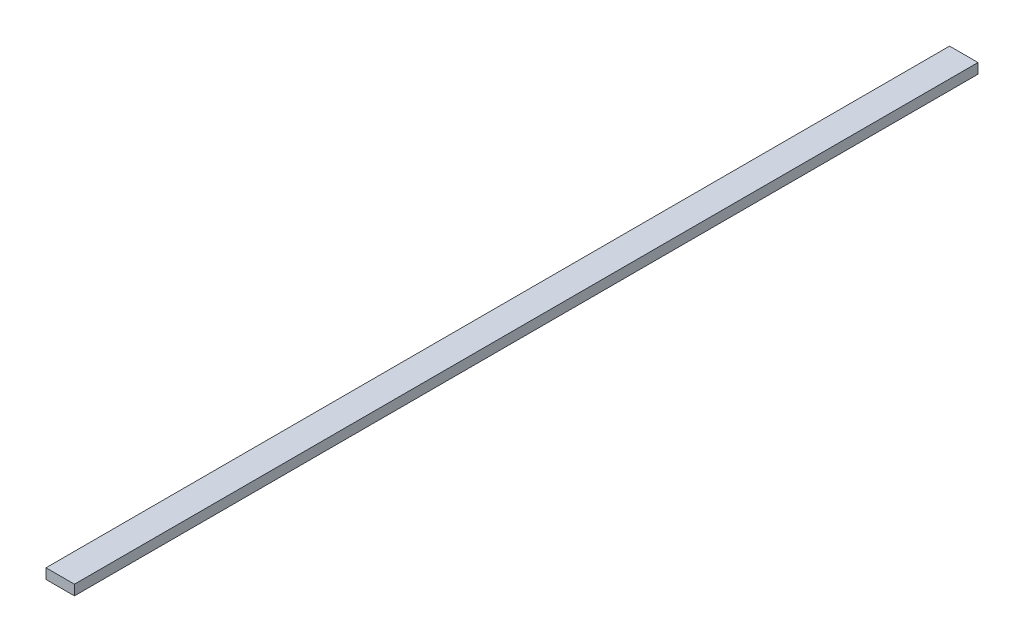
SolidWorks part; units mm, degrees
ref_plane "Ebene vorne" through (0, 0, 0) normal (0, 0, 1) x (1, 0, 0)
ref_plane "Ebene oben" through (0, 0, 0) normal (0, 1, 0) x (1, 0, 0)
ref_plane "Ebene rechts" through (0, 0, 0) normal (1, 0, 0) x (0, 0, -1)
sketch "Skizze1" plane through (0, 0, 0) normal (0, 0, 1) x (1, 0, 0)
  line L1 (0, 0) -> (14, 0)
  line L2 (0, 0) -> (0, 5)
  line L3 (0, 5) -> (14, 5)
  line L4 (14, 0) -> (14, 5)
  dimension "D1" = 5
  dimension "D2" = 14
extrude "Aufsatz-Linear austragen1" add sketch "Skizze1" along normal blind 445
